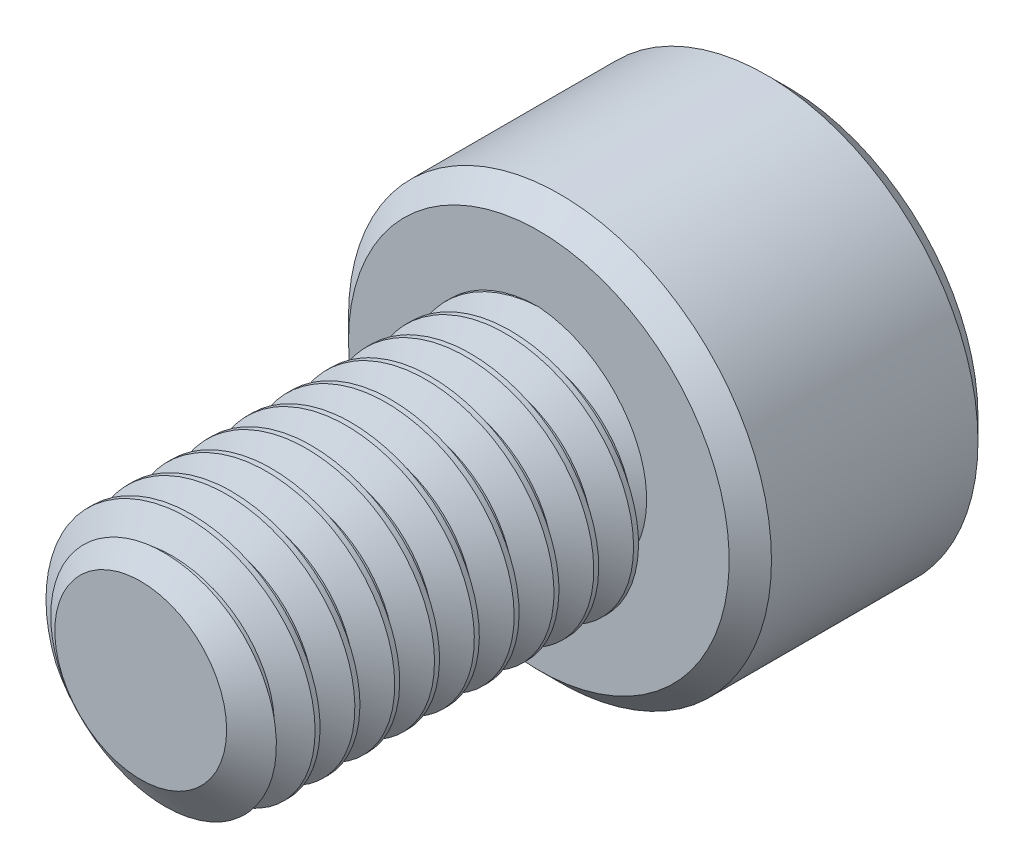
SolidWorks part; units mm, degrees
other "DetailItem1"
ref_plane "Front Plane" through (0, 0, 0) normal (0, 0, 1) x (1, 0, 0)
ref_plane "Top Plane" through (0, 0, 0) normal (0, 1, 0) x (1, 0, 0)
ref_plane "Right Plane" through (0, 0, 0) normal (1, 0, 0) x (0, 0, -1)
sketch "Sketch1" plane through (0, 0, 0) normal (0, 0, 1) x (1, 0, 0)
  circle A0 centre (0, 0) radius 2.5
  dimension "OD" = 5
extrude "Extrude1" add sketch "Sketch1" against normal blind 8
sketch "Sketch2" plane through (0, 0, 0) normal (0, 0, 1) x (1, 0, 0)
  circle A0 centre (0, 0) radius 2.5 construction
  circle A1 centre (0, 0) radius 2.5
curve "Helix/Spiral1" pitch 0.8 height 8.8 turns 11 parameters "pitch"=0.8
sketch "Sketch3" plane through (0, 0, 0) normal (1, 0, 0) x (0, 0, -1)
  line L0 (-0.7, 2.5) -> (-0.4, 1.9804)
  line L1 (-0.4, 1.9804) -> (-0.3, 1.9804)
  line L2 (-0.3, 1.9804) -> (0, 2.5)
  line L3 (-0.7, 2.5) -> (0, 2.5)
  line L4 (-0.35, 2.5) -> (-0.35, 1.9804) construction
  line L5 (-0.55, 2.2402) -> (-0.15, 2.2402) construction
  line L6 (0, 2.5) -> (0, -2.5) construction
  dimension "D1" = 0.1
  dimension "D2" = 0.4
  dimension "D3" = 60
sweep "Cut-Sweep1" cut profiles "Sketch3" path "Helix/Spiral1"
sketch "Sketch4" plane through (0, 0, 0) normal (1, 0, 0) x (0, 0, -1)
  line L0 (0.5417, 2.5) -> (0, 1.7264)
  line L1 (0, 1.7264) -> (0, 2.5)
  line L2 (0.5417, 2.5) -> (0, 2.5)
  line L3 (-0.7, 2.5) -> (0, 2.5) construction
  line L4 (0, 0) -> (7.0209, 0) construction
  dimension "D1" = 55
  dimension "D2" = 0.254
revolve "Cut-Revolve1" cut sketch "Sketch4" angle 360 about L4
sketch "Sketch6" plane through (0, 0, -8) normal (0, 0, -1) x (-1, 0, 0)
  circle A0 centre (0, 0) radius 4.25
  dimension "head dia" = 8.5
extrude "Extrude2" add sketch "Sketch6" along normal blind 5
sketch "Sketch7" plane through (0, 0, -13) normal (0, 0, -1) x (-1, 0, 0)
  line L1 (0, 2.3094) -> (-2, 1.1547)
  line L2 (-2, 1.1547) -> (-2, -1.1547)
  line L3 (-2, -1.1547) -> (0, -2.3094)
  line L4 (0, -2.3094) -> (2, -1.1547)
  line L5 (2, -1.1547) -> (2, 1.1547)
  line L6 (2, 1.1547) -> (0, 2.3094)
  circle A0 centre (0, 0) radius 2 construction
  dimension "hex dia" = 4
extrude "Cut-Extrude1" cut sketch "Sketch7" against normal blind 3
sketch "Sketch8" plane through (0, 0, -13) normal (0, 0, -1) x (-1, 0, 0)
  circle A0 centre (0, 0) radius 2.3094
extrude "Cut-Extrude2" cut sketch "Sketch8" against normal through all draft 45
chamfer "Chamfer1" distance 0.425 angle 45 2 edges at (-4.25, 0, -13) (-4.25, 0, -8)
sketch "Sketch10" plane through (0, 0, -8) normal (0, 0, 1) x (1, 0, 0)
  circle A1 centre (0, 0) radius 2.5
  circle A2 centre (0, 0) radius 2.5
  dimension "D1" = 0
ref_plane "Plane1" through (0, 0, 0) normal (0, 0, 1) x (1, 0, 0)
extrude "partial thread" [suppressed] add sketch "Sketch10" along normal up to surface (13 mm away) separate body
chamfer "Chamfer2" [suppressed] distance 0.1 angle 45
combine bodies "Combine1" [suppressed] operation type add bodies to combine 107 108
sketch "Sketch9" plane through (0, 0, 0) normal (1, 0, 0) x (0, 0, -1)
  line L0 (0, 2.5) -> (0, -2.5) construction
  line L1 (2, 2.5) -> (2, -2.5) construction
  dimension "D1" = 2
equation "\"D3@Helix/Spiral1\" = \"screw length@Extrude1\"+\"pitch@Helix/Spiral1\""
equation "\"D1@Sketch3\" = \"pitch@Helix/Spiral1\"*.125"
equation "\"D2@Sketch3\" = \"pitch@Helix/Spiral1\"*.5"
equation "\"D1@Cut-Extrude1\" = \"hex dia@Sketch7\"*.75"
equation "\"D1@Chamfer1\" = \"head dia@Sketch6\"*.05"
equation "\"D1@Sketch9\" = \"pitch@Helix/Spiral1\"*2.5"
equation "\"D1@Chamfer2\"=\"OD@Sketch1\"*.02"
